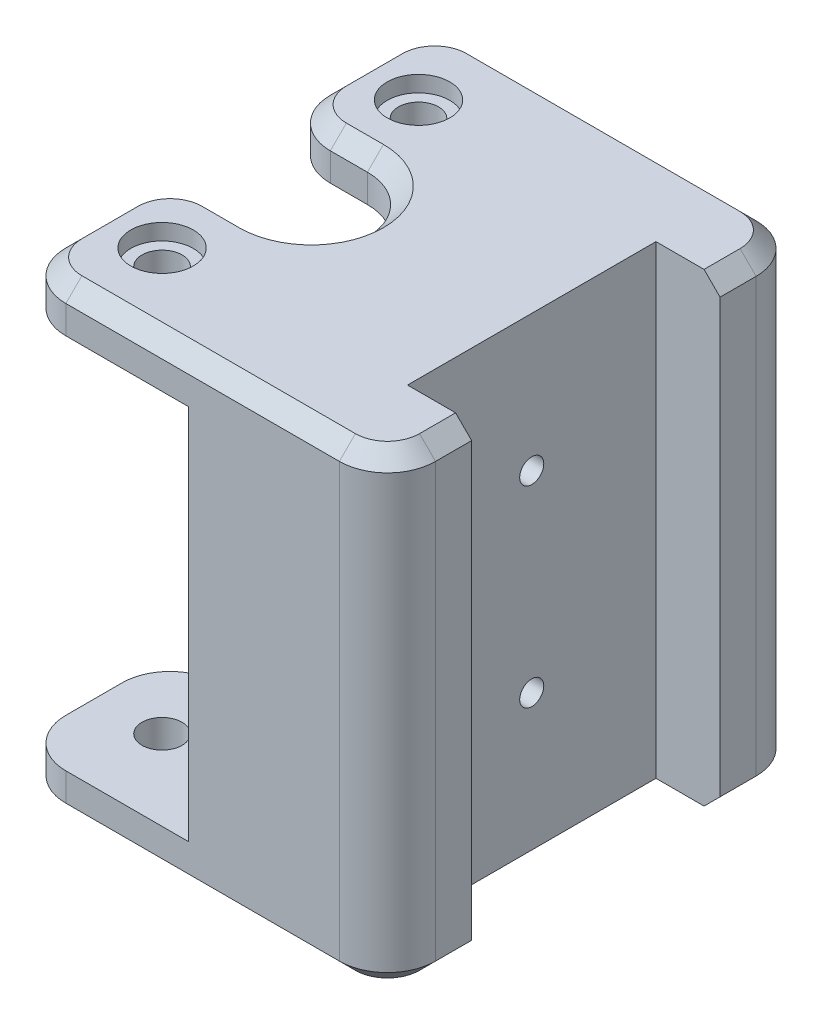
SolidWorks part; units mm, degrees
ref_plane "Спереди" through (0, 0, 0) normal (0, 0, 1) x (1, 0, 0)
ref_plane "Сверху" through (0, 0, 0) normal (0, 1, 0) x (1, 0, 0)
ref_plane "Справа" through (0, 0, 0) normal (1, 0, 0) x (0, 0, -1)
sketch "Эскиз2" plane through (0, 0, 0) normal (0, 1, 0) x (1, 0, 0)
  line L0 (23.6854, 8) -> (23.6854, -8) construction
  line L2 (19.6854, 13) -> (42.75, 13)
  line L3 (19.6854, 13) -> (19.6854, -13)
  line L4 (19.6854, -13) -> (42.75, -13)
  line L5 (42.75, 13) -> (42.75, -13)
  line L6 (19.6854, 13) -> (42.75, -13) construction
  line L7 (19.6854, -13) -> (42.75, 13) construction
  circle A0 centre (0, 0) radius 25 construction
  circle A1 centre (23.6854, 8) radius 1.25
  circle A2 centre (23.6854, -8) radius 1.25
  point P7 (31.2177, 0)
  dimension "D1" = 50
  dimension "D3" = 2.5
  dimension "D4" = 2.5
  dimension "D2" = 16
  dimension "D5" = 4
  dimension "D6" = 42.75
  dimension "D7" = 26
extrude "Бобышка-Вытянуть1" add sketch "Эскиз2" along normal mid plane 29
sketch "Эскиз3" plane through (0, 0, 0) normal (0, 1, 0) x (1, 0, 0)
  circle A0 centre (0, 0) radius 33
  dimension "D1" = 66
extrude "Вырез-Вытянуть1" cut sketch "Эскиз3" against normal mid plane 23.5
sketch "Эскиз4" plane through (0, 14.5, 0) normal (0, 1, 0) x (1, 0, 0)
  line L0 (25, 3.5) -> (19.6854, 3.5)
  line L1 (19.6854, 13) -> (19.6854, -13) construction
  line L2 (19.6854, 3.5) -> (19.6854, -3.5)
  line L3 (19.6854, -3.5) -> (25, -3.5)
  circle A0 centre (0, 0) radius 25 construction
  circle A1 centre (25, 0) radius 3.5
  line M6 (19.6854, 13) -> (19.6854, -13)
  dimension "D1" = 7
extrude "Вырез-Вытянуть2" cut sketch "Эскиз4" against normal through all contours A1 | A1 L0 L3 M6 region at (21.0872, 14.5, 0) region at (25, 14.5, 0)
sketch "Эскиз5" plane through (42.75, 0, 0) normal (1, 0, 0) x (0, 0, -1)
  line L0 (-13, -14.5) -> (13, -14.5) construction
  line L1 (-7.75, 14.5) -> (7.75, 14.5)
  line L2 (-7.75, 14.5) -> (-7.75, -14.5)
  line L3 (-7.75, -14.5) -> (7.75, -14.5)
  line L4 (7.75, 14.5) -> (7.75, -14.5)
  line L5 (-7.75, 14.5) -> (7.75, -14.5) construction
  line L6 (-7.75, -14.5) -> (7.75, 14.5) construction
  point P0 (0, 0)
  dimension "D1" = 15.5
extrude "Вырез-Вытянуть3" cut sketch "Эскиз5" against normal blind 4
fillet "Скругление1" radius 3 10 edges at (42.75, 0, -13) (19.6854, -13.125, -13) (19.6854, -13.125, -3.5) (19.6854, -13.125, 3.5) (19.6854, -13.125, 13) (19.6854, 13.125, -13) (19.6854, 13.125, -3.5) (19.6854, 13.125, 3.5) (19.6854, 13.125, 13) (42.75, 0, 13)
sketch "Эскиз6" plane through (38.75, 0, 0) normal (1, 0, 0) x (0, 0, -1)
  line L0 (-7.75, 0) -> (7.75, 0) construction
  line L1 (-7.75, 14.5) -> (-7.75, -14.5) construction
  line L2 (7.75, -14.5) -> (7.75, 14.5) construction
  circle A0 centre (0, 6) radius 0.75
  circle A1 centre (0, -6) radius 0.75
  point P12 (0, 0)
  dimension "D2" = 1.5
  dimension "D1" = 12
extrude "Вырез-Вытянуть4" cut sketch "Эскиз6" against normal through all
chamfer "Фаска1" distance 1 angle 45 30 edges at (42.75, -14.5, -8.875) (41.8713, -14.5, -12.1213) (31.2177, -14.5, -13) (20.5641, -14.5, -12.1213) (19.6854, -14.5, -8.25) (20.5641, -14.5, -4.3787) (23.8427, -14.5, -3.5) (28.5, -14.5, 0) (23.8427, -14.5, 3.5) (20.5641, -14.5, 4.3787) (19.6854, -14.5, 8.25) (42.75, -14.5, 8.875) (20.5641, -14.5, 12.1213) (41.8713, -14.5, 12.1213) (31.2177, -14.5, 13) (42.75, 14.5, -8.875) (41.8713, 14.5, -12.1213) (31.2177, 14.5, -13) (20.5641, 14.5, -12.1213) (19.6854, 14.5, -8.25) (20.5641, 14.5, -4.3787) (23.8427, 14.5, -3.5) (28.5, 14.5, 0) (23.8427, 14.5, 3.5) (20.5641, 14.5, 4.3787) (19.6854, 14.5, 8.25) (42.75, 14.5, 8.875) (20.5641, 14.5, 12.1213) (41.8713, 14.5, 12.1213) (31.2177, 14.5, 13)
sketch "Эскиз7" plane through (0, 14.5, 0) normal (0, 1, 0) x (1, 0, 0)
  circle A0 centre (23.6854, 8) radius 1.95
  circle A1 centre (23.6854, -8) radius 1.95
  dimension "D1" = 3.9
  dimension "D2" = 3.9
extrude "Вырез-Вытянуть5" cut sketch "Эскиз7" against normal blind 1
mirror "Зеркальное отражение1" about plane through (0, 0, 0) normal (0, 1, 0) of "Вырез-Вытянуть5"
equation "\"motor_diameter\"= 30"
equation "\"mm_diameter\"= IIF ( \"motor_diameter\" < 34 , 41 , \"motor_diameter\" + 8 )"
equation "\"upper_shafts_diameter\"= 5"
equation "\"upper_shats_length\"= 180"
equation "\"upper_bearing_d1\"= 10"
equation "\"upper_bearing_d2\"= 5"
equation "\"upper_bearing_h\"= 15"
equation "\"lower_shafts_diameter\"= 5"
equation "\"lower_shafts_length\"= 180"
equation "\"lower_bearing_d1\"= 10"
equation "\"lower_bearing_d2\"= 5"
equation "\"lower_bearing_h\"= 15"
equation "\"print_offset\"= 0.5"
equation "\"bh_screws_d\"= 2"
equation "\"bh_screws_h\"= 20"
equation "\"bh_screws_hh_d\"= 3.4"
equation "\"bh_screws_hh_h\"= 2"
equation "\"bh_nut_d\"= 3.8"
equation "\"bh_nut_h\"= 2"
equation "\"motor_screws_d\"= 3"
equation "\"motor_screws_h\"= 16"
equation "\"motor_screws_hh_d\"= 5.5"
equation "\"motor_screws_hh_h\"= 3"
equation "\"plate_hole_distance\"= 25.4"
equation "\"plate_screws_d\"= 6.5"
equation "\"shafts_diameter\"= IIF ( \"mm_diameter\" < 42 , 42 + 8 , \"mm_diameter\" + 8 )"
equation "\"central_hole_diameter\"= 8"
equation "\"bh_thikness\"= 4"
equation "\"ends_screws_d\"= 4"
equation "\"ends_screws_h\"= 16"
equation "\"ends_screws_hh_d\"= 6.7"
equation "\"ends_screws_hh_h\"= 4.1"
equation "\"ends_nut_d\"= 6.8"
equation "\"ends_nut_h\"= 3"
equation "\"system_radius\" = ( \"shafts_diameter\" + 12 + \"bh_thikness\" / 2 ) / 2"
equation "\"encoder_distance\"= \"system_radius\" + 4"
equation "\"tape_position\"= \"encoder_distance\" - 2 + 3.9 + 1.7 / 2"
equation "\"D1@Эскиз2\"=\"shafts_diameter\""
equation "\"D3@Эскиз2\"=\"bh_screws_d\"+\"print_offset\""
equation "\"D4@Эскиз2\"=\"D3@Эскиз2\""
equation "\"D5@Эскиз2\"=\"bh_thikness\""
equation "\"D6@Эскиз2\"=\"tape_position\"+4"
equation "\"D1@Бобышка-Вытянуть1\"=\"lower_bearing_h\"+\"bh_thikness\"*2+6"
equation "\"D1@Эскиз3\"=\"system_radius\"*2+2"
equation "\"D1@Вырез-Вытянуть1\"=\"lower_bearing_h\"+\"bh_thikness\"*2+\"print_offset\""
equation "\"D1@Эскиз4\"=\"lower_shafts_diameter\"+2"
equation "\"D1@Эскиз5\"=\"print_offset\"+15"
equation "\"D2@Эскиз6\"=\"bh_screws_d\"-\"print_offset\""
equation "\"D1@Эскиз7\"=\"bh_screws_hh_d\"+\"print_offset\""
equation "\"D2@Эскиз7\"=\"D1@Эскиз7\""
